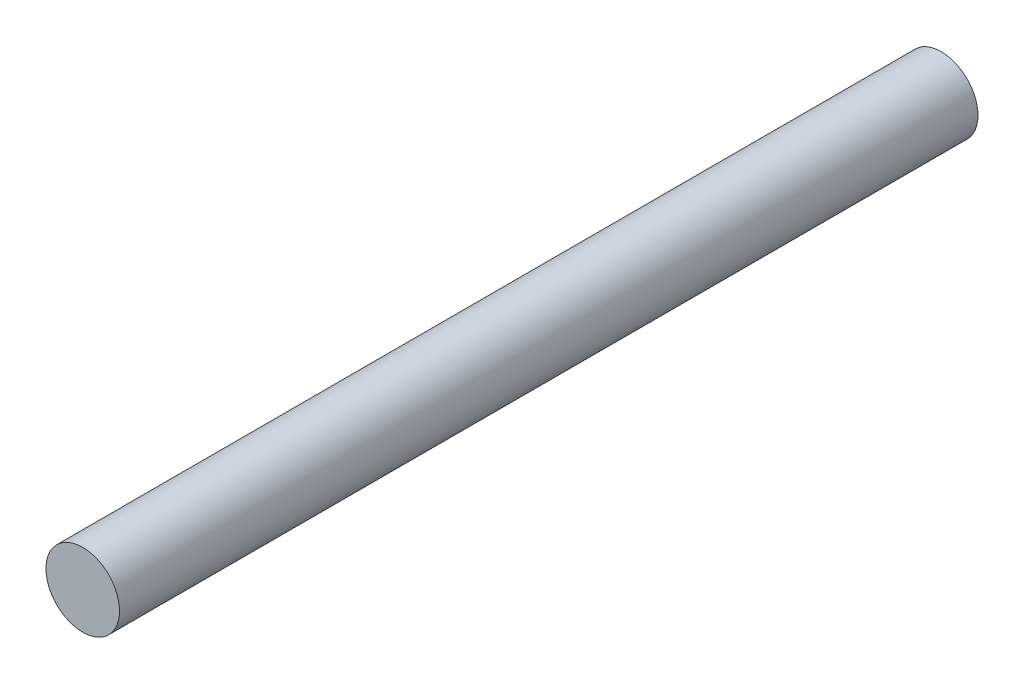
SolidWorks part; units mm, degrees
ref_plane "Alzado" through (0, 0, 0) normal (0, 0, 1) x (1, 0, 0)
ref_plane "Planta" through (0, 0, 0) normal (0, 1, 0) x (1, 0, 0)
ref_plane "Vista lateral" through (0, 0, 0) normal (1, 0, 0) x (0, 0, -1)
sketch "Croquis1" plane through (0, 0, 0) normal (0, 0, 1) x (1, 0, 0)
  circle A0 centre (0, 0) radius 1.5
  dimension "D1" = 3
extrude "Saliente-Extruir1" add sketch "Croquis1" against normal blind 35
